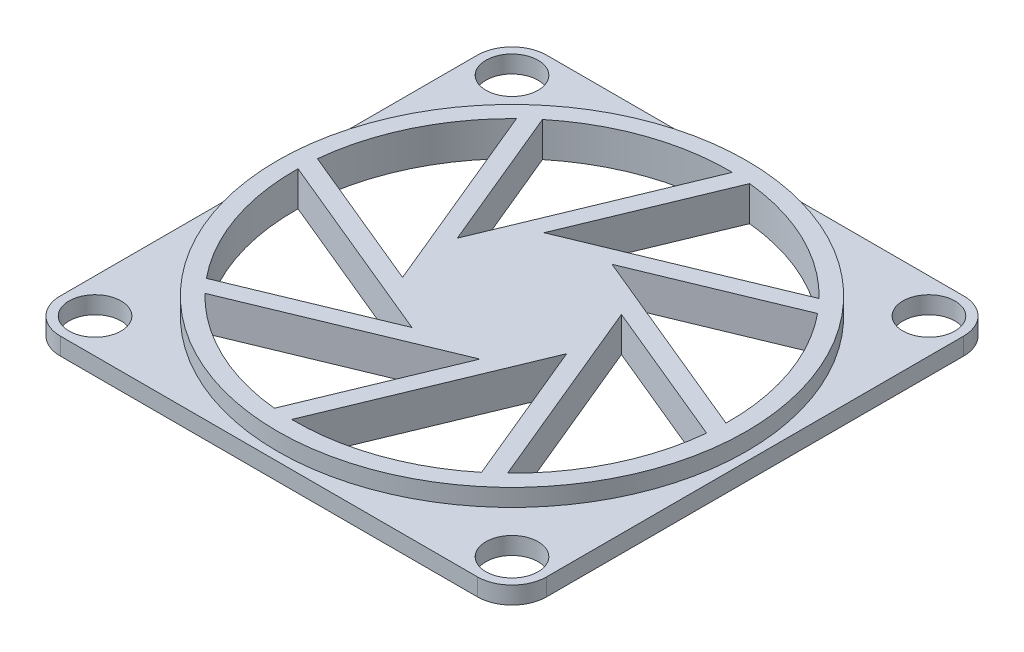
SolidWorks part; units mm, degrees
ref_plane "Front Plane" through (0, 0, 0) normal (0, 0, 1) x (1, 0, 0)
ref_plane "Top Plane" through (0, 0, 0) normal (0, 1, 0) x (1, 0, 0)
ref_plane "Right Plane" through (0, 0, 0) normal (1, 0, 0) x (0, 0, -1)
sketch "Sketch1" plane through (0, 0, 0) normal (0, 1, 0) x (1, 0, 0)
  line L0 (-12, -14) -> (12, -14)
  line L1 (-12, 15) -> (12, 15) construction
  line L2 (-15, 12) -> (-15, -12) construction
  line L3 (-12, -15) -> (12, -15) construction
  line L4 (15, 12) -> (15, -12) construction
  line L5 (14, 12) -> (14, -12)
  line L6 (-12, 14) -> (12, 14)
  line L7 (-14, 12) -> (-14, -12)
  circle A0 centre (0, 0) radius 15 construction
  arc A1 (12, -15) -> (15, -12) centre (12, -12) ccw construction
  arc A2 (15, 12) -> (12, 15) centre (12, 12) ccw construction
  arc A3 (-12, 15) -> (-15, 12) centre (-12, 12) ccw construction
  arc A4 (-12, -15) -> (-15, -12) centre (-12, -12) cw construction
  circle A5 centre (0, 0) radius 12.5
  arc A6 (12, -14) -> (14, -12) centre (12, -12) ccw
  arc A7 (14, 12) -> (12, 14) centre (12, 12) ccw
  arc A8 (-12, 14) -> (-14, 12) centre (-12, 12) ccw
  arc A9 (-12, -14) -> (-14, -12) centre (-12, -12) cw
  circle A10 centre (-12, 12) radius 1.5
  circle A11 centre (12, 12) radius 1.5
  circle A12 centre (12, -12) radius 1.5
  circle A13 centre (-12, -12) radius 1.5
  point P9 (15, -15)
  point P16 (-15, -15)
  dimension "D2" = 3
  dimension "D3" = 25
  dimension "D5" = 3
  dimension "D1" = 30
  dimension "D4" = 1
extrude "Boss-Extrude1" add sketch "Sketch1" along normal blind 1
sketch "Sketch3" plane through (0, 1, 0) normal (0, 1, 0) x (1, 0, 0)
  circle A1 centre (0, 0) radius 12.5
  circle A2 centre (0, 0) radius 12.5 construction
  circle A3 centre (0, 0) radius 13.5
  dimension "D1" = 1
extrude "Boss-Extrude2" add sketch "Sketch3" along normal blind 1
sketch "Sketch4" plane through (0, 0, 0) normal (0, 1, 0) x (1, 0, 0)
  line L0 (0, 9.0295) -> (0, -6.7102) construction
  line L1 (-3.5322, 3.5322) -> (-4.9952, 0) construction
  line L2 (-4.9952, 0) -> (-3.5322, -3.5322) construction
  line L3 (-3.5322, -3.5322) -> (0, -4.9952) construction
  line L4 (0, -4.9952) -> (3.5322, -3.5322) construction
  line L5 (3.5322, -3.5322) -> (4.9952, 0) construction
  line L6 (4.9952, 0) -> (3.5322, 3.5322) construction
  line L7 (3.5322, 3.5322) -> (0, 4.9952) construction
  line L8 (0, 4.9952) -> (-3.5322, 3.5322) construction
  line L9 (-3.5322, 3.5322) -> (8.9665, 8.7093) construction
  line L10 (0, 4.9952) -> (12.4987, -0.1819) construction
  line L11 (3.5322, 3.5322) -> (8.7093, -8.9665) construction
  line L12 (4.9952, 0) -> (-0.1819, -12.4987) construction
  line L13 (3.5322, -3.5322) -> (-8.9665, -8.7093) construction
  line L14 (-12.4987, 0.1819) -> (0, -4.9952) construction
  line L15 (-8.7093, 8.9665) -> (-3.5322, -3.5322) construction
  line L16 (0.1819, 12.4987) -> (-4.9952, 0) construction
  line L17 (1.1058, 12.116) -> (-4.0714, -0.3827) construction
  line L18 (-3.1495, 2.6083) -> (9.3492, 7.7854) construction
  line L19 (-0.3827, 4.0714) -> (12.116, -1.1058) construction
  line L20 (2.6083, 3.1495) -> (7.7854, -9.3492) construction
  line L21 (3.1495, -2.6083) -> (-9.3492, -7.7854) construction
  line L22 (-12.116, 1.1058) -> (0.3827, -4.0714) construction
  line L23 (-7.7854, 9.3492) -> (-2.6083, -3.1495) construction
  line L24 (-4.454, 1.3066) -> (0.1819, 12.4987)
  line L25 (1.2393, 12.4384) -> (-2.2256, 4.0734)
  line L26 (-2.2256, 4.0734) -> (8.9665, 8.7093)
  line L27 (9.6716, 7.919) -> (1.3066, 4.454)
  line L28 (1.3066, 4.454) -> (12.4987, -0.1819)
  line L29 (12.4384, -1.2393) -> (4.0734, 2.2256)
  line L30 (4.0734, 2.2256) -> (8.7093, -8.9665)
  line L31 (7.919, -9.6716) -> (4.454, -1.3066)
  line L32 (4.454, -1.3066) -> (-0.1819, -12.4987)
  line L33 (4.0714, 0.3827) -> (-1.1058, -12.116) construction
  line L34 (-1.2393, -12.4384) -> (2.2256, -4.0734)
  line L35 (2.2256, -4.0734) -> (-8.9665, -8.7093)
  line L36 (-9.6716, -7.919) -> (-1.3066, -4.454)
  line L37 (-1.3066, -4.454) -> (-12.4987, 0.1819)
  line L38 (-12.4384, 1.2393) -> (-4.0734, -2.2256)
  line L39 (-4.0734, -2.2256) -> (-8.7093, 8.9665)
  line L40 (-7.919, 9.6716) -> (-4.454, 1.3066)
  circle A0 centre (0, 0) radius 4.615 construction
  circle A1 centre (0, 0) radius 12.5 construction
  arc A2 (-8.7093, 8.9665) -> (-7.919, 9.6716) centre (0, 0) cw
  arc A3 (0.1819, 12.4987) -> (1.2393, 12.4384) centre (0, 0) cw
  arc A4 (8.9665, 8.7093) -> (9.6716, 7.919) centre (0, 0) cw
  arc A5 (12.4987, -0.1819) -> (12.4384, -1.2393) centre (0, 0) cw
  arc A6 (8.7093, -8.9665) -> (7.919, -9.6716) centre (0, 0) cw
  arc A8 (-8.9665, -8.7093) -> (-9.6716, -7.919) centre (0, 0) cw
  arc A9 (-12.4987, 0.1819) -> (-12.4384, 1.2393) centre (0, 0) cw
  arc A10 (-1.2393, -12.4384) -> (-0.1819, -12.4987) centre (0, 0) ccw
  dimension "D1" = 9.23
  dimension "D2" = 1
  dimension "D3" = 1
  dimension "D4" = 1
  dimension "D5" = 1
  dimension "D6" = 1
  dimension "D7" = 1
  dimension "D8" = 1
  dimension "D9" = 1
extrude "Boss-Extrude3" add sketch "Sketch4" along normal up to surface (2 mm away) up to face at (0, 2, 13.5)
